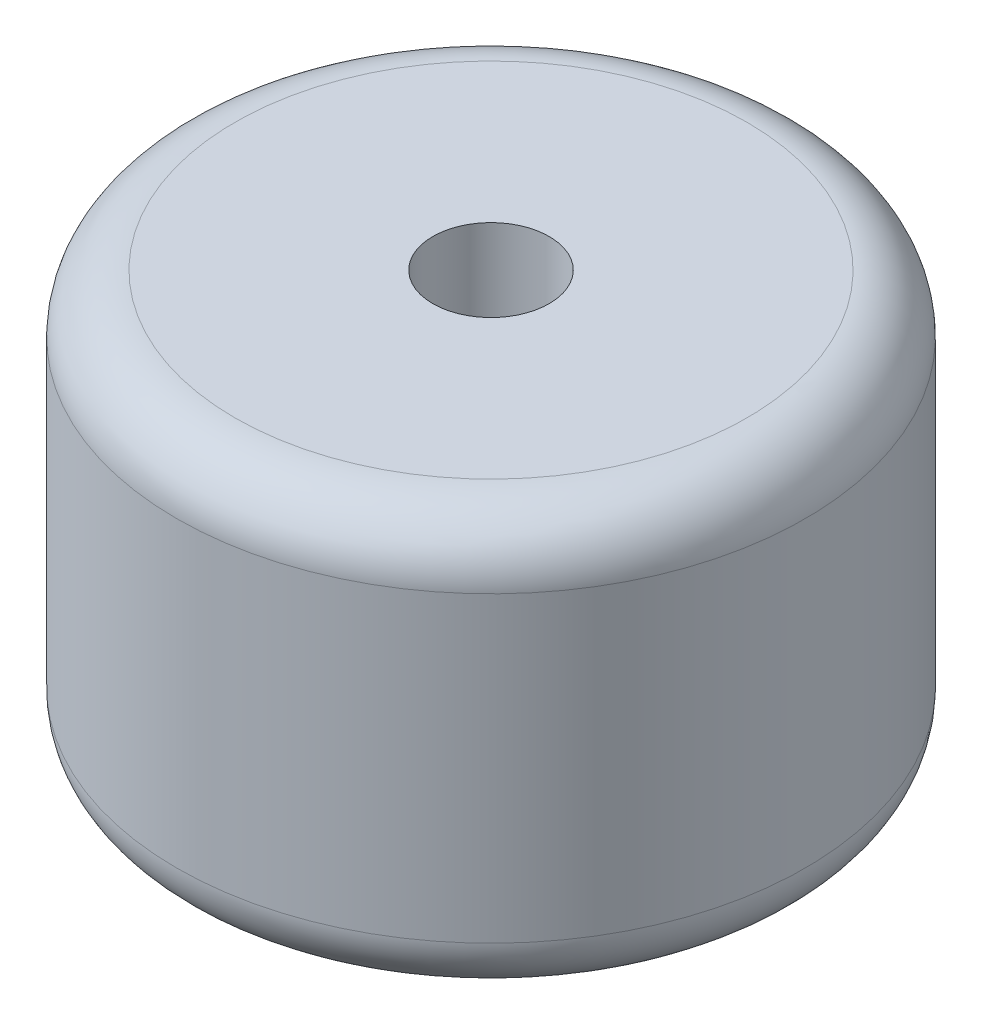
SolidWorks part; units mm, degrees
ref_plane "Alzado" through (0, 0, 0) normal (0, 0, 1) x (1, 0, 0)
ref_plane "Planta" through (0, 0, 0) normal (0, 1, 0) x (1, 0, 0)
ref_plane "Vista lateral" through (0, 0, 0) normal (1, 0, 0) x (0, 0, -1)
sketch "Croquis1" plane through (0, 0, 0) normal (0, 1, 0) x (1, 0, 0)
  circle A0 centre (0, 0) radius 27
  circle A1 centre (0, 0) radius 5
  dimension "D1" = 54
  dimension "D2" = 10
extrude "Saliente-Extruir1" add sketch "Croquis1" along normal blind 36
fillet "Redondeo1" radius 5 2 edges at (0, 0, 27) (0, 36, 27)
